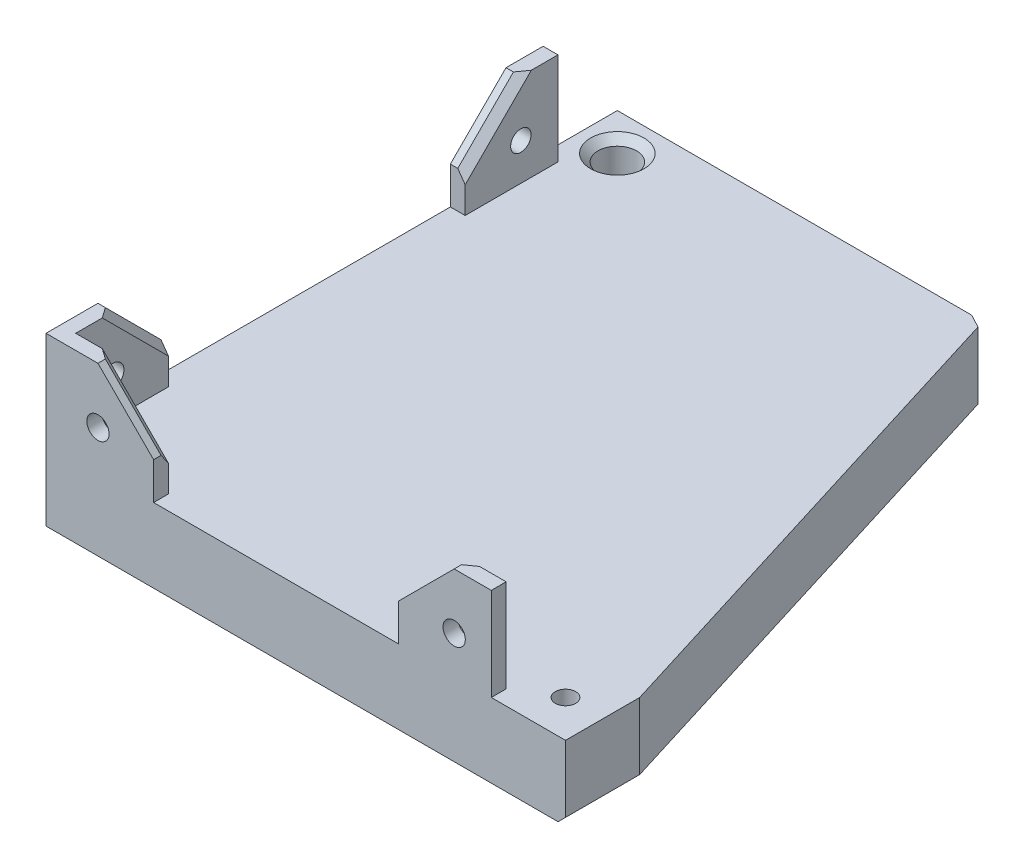
SolidWorks part; units mm, degrees
ref_plane "Front Plane" through (0, 0, 0) normal (0, 0, 1) x (1, 0, 0)
ref_plane "Top Plane" through (0, 0, 0) normal (0, 1, 0) x (1, 0, 0)
ref_plane "Right Plane" through (0, 0, 0) normal (1, 0, 0) x (0, 0, -1)
sketch "Sketch1" plane through (0, 0, 0) normal (0, 1, 0) x (1, 0, 0)
  line L0 (-5, 5) -> (-22.101, 51.9846)
  line L1 (-5, -5) -> (5, -5)
  line L2 (-5, -5) -> (-5, 5)
  line L3 (-5, 5) -> (5, 5)
  line L4 (5, -5) -> (5, 5)
  line L5 (-5, -5) -> (5, 5) construction
  line L6 (-5, 5) -> (5, -5) construction
  line L7 (5, 5) -> (-12.5931, 61.819)
  line L8 (-22.101, 51.9846) -> (-32.101, 51.9846)
  line L9 (-22.101, 51.9846) -> (-22.101, 71.9846)
  line L10 (-22.101, 71.9846) -> (-32.101, 71.9846)
  line L11 (-32.101, 51.9846) -> (-32.101, 71.9846)
  line L12 (-12.5931, 61.819) -> (-15.7407, 71.9846)
  line L13 (-15.7407, 71.9846) -> (-22.101, 71.9846)
  line L14 (-5, -5) -> (-65, -5)
  line L15 (-65, -5) -> (-65, 71.9846)
  line L16 (-65, 71.9846) -> (-32.101, 71.9846)
  point P0 (0, 0)
  dimension "D1" = 10
  dimension "D2" = 10
  dimension "D3" = 10
  dimension "D4" = 20
extrude "Boss-Extrude1" add sketch "Sketch1" along normal blind 10 contours L12 L13 L9 L0 L3 L7 | L11 L8 L9 L10 | L16 L15 L14 L2 L0 L8 L11 | L1 L4 L3 L2 region at (-40.0821, 0, -28.981) region at (0, 0, 0) region at (-10.5765, 0, -37.6691) region at (-27.101, 0, -61.9846)
sketch "Sketch2" plane through (0, 10, 0) normal (0, 1, 0) x (1, 0, 0)
  line L0 (-5, -5) -> (5, -5)
  line L1 (-65, -5) -> (-50.5, -5)
  line L2 (-65, -5) -> (-65, -3)
  line L3 (-65, -3) -> (-50.5, -3)
  line L4 (-50.5, -5) -> (-50.5, -3)
  line L5 (5, -5) -> (-65, -5) construction
  line L7 (-17.5, -5) -> (-5, -5)
  line L8 (-17.5, -5) -> (-17.5, -3)
  line L9 (-17.5, -3) -> (-5, -3)
  line L10 (-5, -5) -> (-5, -3)
  line L11 (-65, -5) -> (-63, -5)
  line L12 (-65, -5) -> (-65, 9.5)
  line L13 (-65, 9.5) -> (-63, 9.5)
  line L14 (-63, -5) -> (-63, 9.5)
  line L15 (-65, -5) -> (-65, 71.9846) construction
  line L16 (-65, 9.5) -> (-65, 49.4846)
  line L17 (-65, 61.9846) -> (-63, 61.9846)
  line L18 (-65, 61.9846) -> (-65, 49.4846)
  line L19 (-65, 49.4846) -> (-63, 49.4846)
  line L20 (-63, 61.9846) -> (-63, 49.4846)
  line L21 (-65, 71.9846) -> (-65, 61.9846)
  line M8 (-65, 71.9846) -> (-65, -5)
  line M9 (-65, -5) -> (5, -5)
  dimension "D1" = 14.5
  dimension "D2" = 10
  dimension "D3" = 12.5
  dimension "D4" = 14.5
  dimension "D5" = 2
  dimension "D6" = 10
  dimension "D7" = 12.5
  dimension "D8" = 2
  dimension "D9" = 2
  dimension "D10" = 2
extrude "Boss-Extrude2" add sketch "Sketch2" along normal blind 12.5 contours L3 L14 L13 M8 | L14 L3 M9 M8 | L14 L1 L4 L3 | L10 L9 L8 M9 | L17 L20 L19 L18 region at (-64, 10, 4) region at (-11.25, 10, 4) region at (-56.75, 10, 4) region at (-64, 10, -3.25)
sketch "Sketch3" plane through (0, 0, 3) normal (0, 0, -1) x (-1, 0, 0)
  line L1 (65, 10) -> (58, 10)
  line L2 (65, 10) -> (65, 15)
  line L3 (65, 15) -> (58, 15)
  line L4 (58, 10) -> (58, 15)
  line L5 (5, 10) -> (10, 10)
  line L6 (5, 10) -> (5, 15)
  line L7 (5, 15) -> (10, 15)
  line L8 (10, 10) -> (10, 15)
  circle A0 centre (10, 15) radius 1.5
  circle A1 centre (58, 15) radius 1.5
  dimension "D1" = 5
  dimension "D2" = 5
  dimension "D3" = 7
  dimension "D4" = 5
extrude "Cut-Extrude1" cut sketch "Sketch3" against normal up to surface (2 mm away) contours A1 | A0 up to face at (-26.6, 13, 5)
chamfer "Chamfer1" distance 7.5 angle 45 2 edges at (-50.5, 22.5, 4) (-17.5, 22.5, 4)
chamfer "Chamfer2" distance 1 angle 45 2 edges at (-13.75, 18.75, 3) (-54.25, 18.75, 3)
sketch "Sketch4" plane through (-63, 0, 0) normal (1, 0, 0) x (0, 0, -1)
  line L1 (-5, 10) -> (2, 10)
  line L2 (-5, 10) -> (-5, 15)
  line L3 (-5, 15) -> (2, 15)
  line L4 (2, 10) -> (2, 15)
  line L9 (61.9846, 10) -> (56.9846, 10)
  line L10 (61.9846, 10) -> (61.9846, 15)
  line L11 (61.9846, 15) -> (56.9846, 15)
  line L12 (56.9846, 10) -> (56.9846, 15)
  circle A0 centre (2, 15) radius 1.5
  circle A2 centre (56.9846, 15) radius 1.375
  dimension "D3" = 7
  dimension "D1" = 5
  dimension "D2" = 5
extrude "Cut-Extrude2" cut sketch "Sketch4" against normal up to surface (2 mm away) contours A0 | A2 up to face at (-65, 13, -37.5908)
chamfer "Chamfer3" distance 7.5 angle 45 2 edges at (-64, 22.5, -9.5) (-64, 22.5, -49.4846)
chamfer "Chamfer4" distance 1 angle 45 2 edges at (-63, 18.75, -5.75) (-63, 18.75, -53.2346)
chamfer "Chamfer5" distance 1 angle 45 3 edges at (5, 0, 0) (-40.3704, 0, -71.9846) (-5.3704, 0, -38.4923)
sketch "Sketch5" plane through (0, 10, 0) normal (0, 1, 0) x (1, 0, 0)
  line L5 (-65, 71.9846) -> (-60, 71.9846)
  line L6 (-65, 71.9846) -> (-65, 66.9846)
  line L7 (-65, 66.9846) -> (-60, 66.9846)
  line L8 (-60, 71.9846) -> (-60, 66.9846)
  circle A1 centre (-60, 66.9846) radius 2.6
  dimension "D3" = 5
  dimension "D4" = 5
extrude "Cut-Extrude3" cut sketch "Sketch5" against normal blind 5 contours A1
chamfer "Chamfer6" distance 1 angle 45 1 edges at (-60, 10, -64.3846)
chamfer "Chamfer7" distance 1 angle 45 1 edges at (-15.7407, 5.5, -71.9846) first distance on face at (-5.3704, 5.5, -38.4923)
sketch "Sketch6" plane through (0, 0, 0) normal (0, -1, 0) x (1, 0, 0)
  line L1 (5, 5) -> (0, 5)
  line L2 (5, 5) -> (5, 0)
  line L3 (5, 0) -> (0, 0)
  line L4 (0, 5) -> (0, 0)
  circle A0 centre (0, 0) radius 2.75
extrude "Cut-Extrude4" cut sketch "Sketch6" against normal blind 5.5 contours A0
sketch "Sketch7" plane through (0, 5.5, 0) normal (0, -1, 0) x (1, 0, 0)
  circle A0 centre (0, 0) radius 1.375
extrude "Cut-Extrude5" cut sketch "Sketch7" against normal up to surface (4.5 mm away) up to face at (-60, 10, -63.3846)
